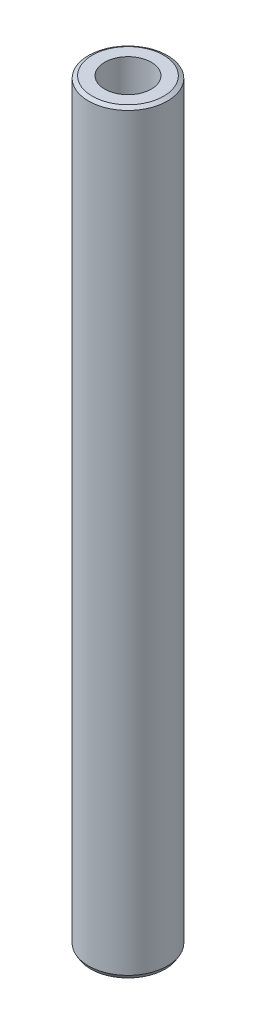
SolidWorks part; units mm, degrees
ref_plane "Front Plane" through (0, 0, 0) normal (0, 0, 1) x (1, 0, 0)
ref_plane "Top Plane" through (0, 0, 0) normal (0, 1, 0) x (1, 0, 0)
ref_plane "Right Plane" through (0, 0, 0) normal (1, 0, 0) x (0, 0, -1)
sketch "Sketch1" plane through (0, 0, 0) normal (0, 1, 0) x (1, 0, 0)
  circle A0 centre (0, 0) radius 10
  dimension "SHAFT_OD" = 20
extrude "Boss-Extrude1" add sketch "Sketch1" along normal blind 191.1787
sketch "Sketch2" plane through (0, 0, 0) normal (0, 1, 0) x (1, 0, 0)
  circle A0 centre (0, 0) radius 5.9038
  dimension "BORE_D" = 11.8075
extrude "Cut-Extrude1" cut sketch "Sketch2" along normal through all
chamfer "Chamfer1" distance 0.5632 angle 60 2 edges at (0, 191.1787, 10) (0, 0, 10) first distance on face at (0, 191.1787, 10) first distance on face at (0, 0, 5.9038)
